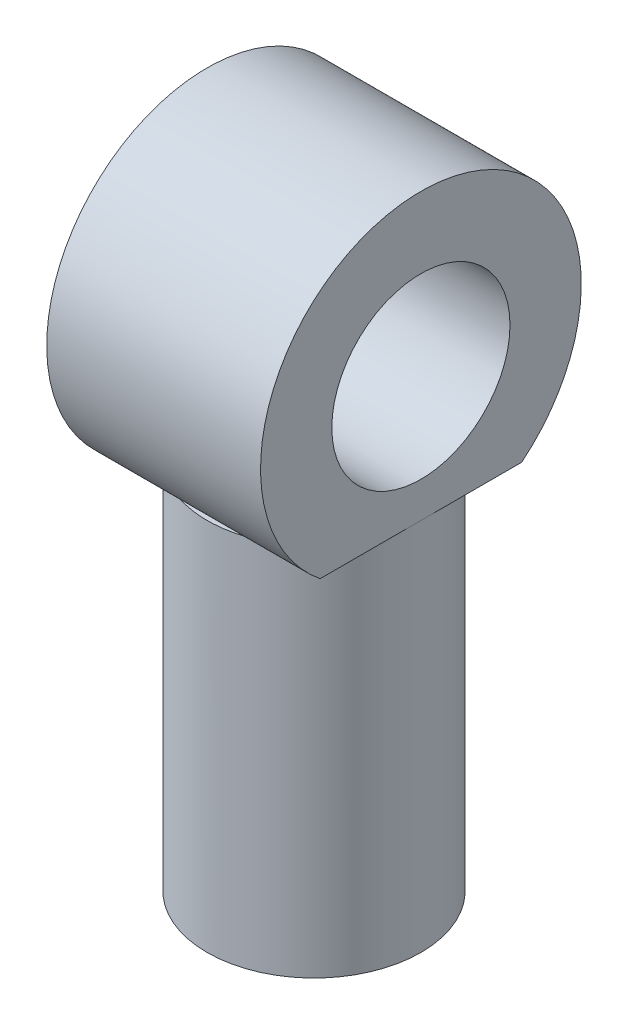
SolidWorks part; units mm, degrees
ref_plane "Front Plane" through (0, 0, 0) normal (0, 0, 1) x (1, 0, 0)
ref_plane "Top Plane" through (0, 0, 0) normal (0, 1, 0) x (1, 0, 0)
ref_plane "Right Plane" through (0, 0, 0) normal (1, 0, 0) x (0, 0, -1)
sketch "Sketch1" plane through (0, 0, 0) normal (0, 1, 0) x (1, 0, 0)
  circle A0 centre (0, 0) radius 3
  dimension "D1" = 6
extrude "crank_body" add sketch "Sketch1" along normal blind 10
sketch "Sketch2" plane through (0, 0, 0) normal (0, -1, 0) x (1, 0, 0)
  circle A0 centre (0, 0) radius 1.55
  dimension "D1" = 3.1
extrude "dowel_shaft" cut sketch "Sketch2" against normal blind 9
sketch "Sketch3" plane through (0, 0, 0) normal (1, 0, 0) x (0, 0, -1)
  line L0 (3, 10) -> (-3, 10) construction
  line L1 (-3, 10) -> (-3, 0) construction
  line L2 (-3, 10) -> (3, 10)
  line L3 (-3, 10) -> (-3, 10.5)
  line L4 (-3, 10.5) -> (3, 10.5)
  line L5 (3, 10) -> (3, 10.5)
  line L6 (3, 0) -> (3, 10) construction
  line L7 (-3, 10) -> (-3, 0) construction
  circle A0 centre (0, 14) radius 4.5
  dimension "D1" = 9
  dimension "D2" = 4
  dimension "D6" = 3
  dimension "D3" = 0.5
  dimension "D4" = 0
  dimension "D5" = 0
extrude "pin_shaft_body" add sketch "Sketch3" along normal blind 3 and the other way blind 3 contours A0 L3 L2 | L3 A0 L5 L4 | L5 A0 L3 L4 | L5 L4 L3 L2 region at (0, 10.1897, 2.6907) region at (0, 10.2628, 0) region at (0, 14.2525, 0)
sketch "Sketch4" plane through (3, 0, 0) normal (1, 0, 0) x (0, 0, -1)
  circle A0 centre (0, 14) radius 2.5
  dimension "D1" = 5
extrude "pin_shaft" cut sketch "Sketch4" against normal through all
extrude "smoothing_cuts" cut sketch "Sketch1<2>" along normal blind 10.5 flip side to cut
sketch "Sketch1<2>" plane through (0, 0, 0) normal (0, 1, 0) x (1, 0, 0) same geometry as "Sketch1"
